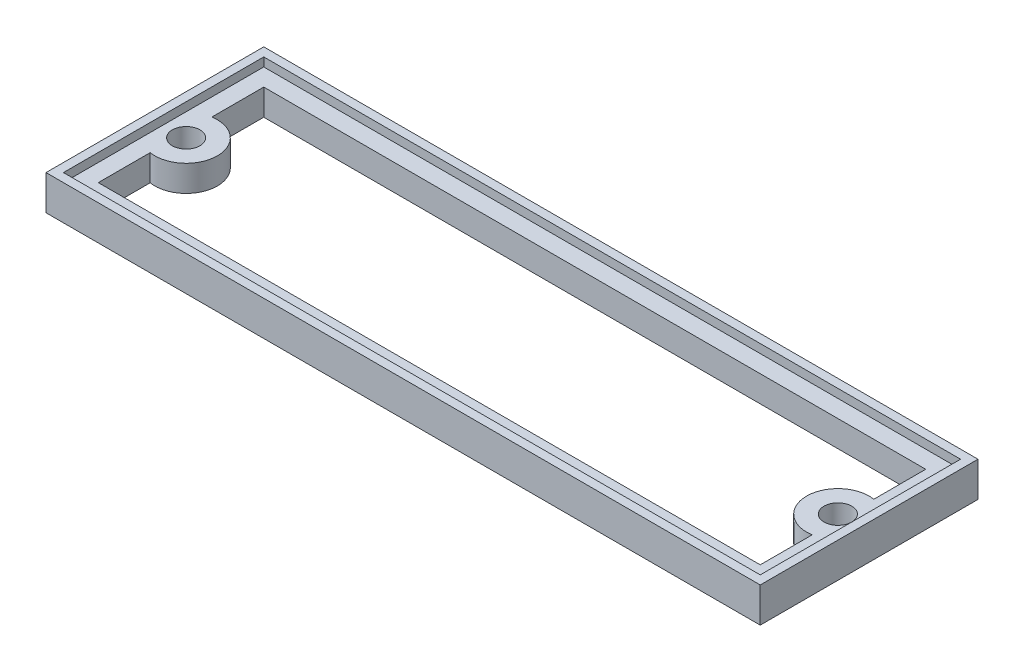
SolidWorks part; units mm, degrees
material "ABS"
ref_plane "Front" through (0, 0, 0) normal (0, 0, 1) x (1, 0, 0)
ref_plane "Top" through (0, 0, 0) normal (0, 1, 0) x (1, 0, 0)
ref_plane "Right" through (0, 0, 0) normal (1, 0, 0) x (0, 0, -1)
sketch "Sketch1" plane through (0, 0, 0) normal (0, 1, 0) x (1, 0, 0)
  line L0 (0, 0) -> (0, 23)
  line L1 (0, 23) -> (80, 23)
  line L2 (80, 23) -> (80, 0)
  line L3 (80, 0) -> (0, 0)
  line L4 (-1, 24) -> (81, 24)
  line L5 (81, 24) -> (81, -1)
  line L6 (81, -1) -> (-1, -1)
  line L7 (-1, -1) -> (-1, 24)
  line L8 (80, 11.5) -> (79, 11.5) construction
  line L9 (40, 22) -> (40, 0) construction
  line L10 (2, 21) -> (78, 21)
  line L11 (78, 21) -> (78, 15.0391)
  line L12 (78, 2) -> (2, 2)
  line L13 (2, 2) -> (2, 7.9609)
  line L14 (2, 15.0391) -> (2, 21)
  line L15 (78, 7.9609) -> (78, 2)
  line L16 (2, 2) -> (2, 21) construction
  line L18 (78, 21) -> (78, 2) construction
  circle A0 centre (77.4125, 11.5) radius 1.5875
  circle A1 centre (2.5875, 11.5) radius 1.5875
  arc A2 (78, 15.0391) -> (78, 7.9609) centre (77.4125, 11.5) ccw
  arc A3 (2, 15.0391) -> (2, 7.9609) centre (2.5875, 11.5) cw
  circle A4 centre (77.4125, 11.5) radius 3.5875 construction
  point P19 (81.35, 11)
  dimension "D8" = 3.175
  dimension "D1" = 80
  dimension "D2" = 23
  dimension "D3" = 1
  dimension "D4" = 25
  dimension "D5" = 1
  dimension "D6" = 82
  dimension "D7" = 1
  dimension "D9" = 40
  dimension "D10" = 2
  dimension "D11" = 2
extrude "Boss-Extrude1" add sketch "Sketch1" along normal blind 3 contours L3 L2 L1 L0 A3 L14 L10 L11 A2 L15 L12 L13 A0 A1 region at (0.8324, 0, -11.5)
extrude "Boss-Extrude2" add sketch "Sketch1<3>" along normal blind 4 contours L7 L6 L5 L4 L2 L3 L0 L1 region at (40, 0, -23.1427)
sketch "Sketch1<3>" plane through (0, 0, 0) normal (0, 1, 0) x (1, 0, 0) same geometry as "Sketch1"
